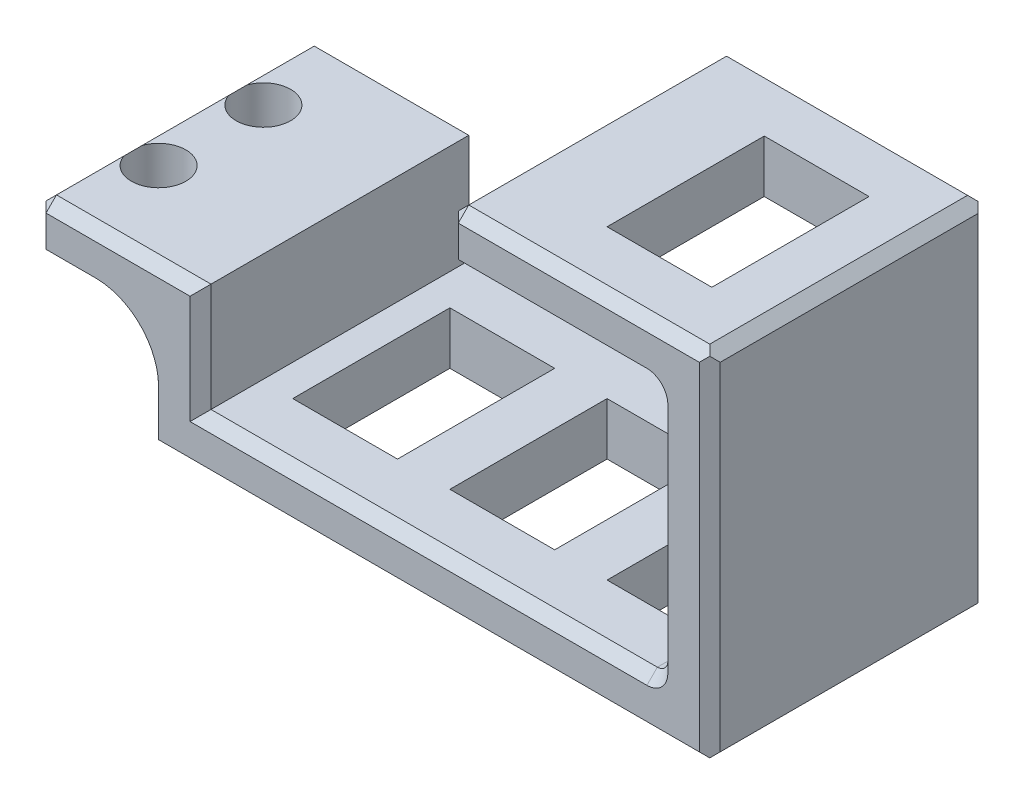
SolidWorks part; units mm, degrees
ref_plane "Alzado" through (0, 0, 0) normal (0, 0, 1) x (1, 0, 0)
ref_plane "Planta" through (0, 0, 0) normal (0, 1, 0) x (1, 0, 0)
ref_plane "Vista lateral" through (0, 0, 0) normal (1, 0, 0) x (0, 0, -1)
sketch "Croquis1" plane through (0, 0, 0) normal (0, 0, 1) x (1, 0, 0)
  line L1 (20.8029, -8) -> (36.55, -8)
  line L2 (20.8029, -8) -> (20.8029, -13)
  line L3 (20.8029, -13) -> (31.55, -13)
  line L6 (80.15, -18.36) -> (85.15, -18.36) construction
  line L8 (31.55, -13) -> (31.55, -23.36)
  line L9 (31.55, -23.36) -> (36.55, -23.36)
  line L10 (36.55, -8) -> (36.55, -18.36)
  line L12 (36.55, -23.36) -> (85.15, -23.36)
  line L14 (36.55, -18.36) -> (80.15, -18.36)
  line L15 (85.15, -23.36) -> (85.15, -18.36)
  line L17 (85.15, -18.36) -> (85.15, 10.84)
  line L18 (85.15, 10.84) -> (80.15, 10.84)
  line L19 (80.15, -18.36) -> (80.15, 5.84)
  line L20 (31.55, -13) -> (36.55, -13) construction
  line L21 (36.55, -23.36) -> (36.55, -18.36) construction
  line L24 (80.15, 10.84) -> (60.15, 10.84)
  line L26 (80.15, 5.84) -> (60.15, 5.84)
  line L27 (60.15, 10.84) -> (60.15, 5.84)
  line L29 (80.15, 10.84) -> (80.15, 5.84) construction
  line L31 (46.55, 5.64) -> (70.15, 5.64) construction
  line L32 (34.55, -8) -> (0, -8) construction
  line L33 (20.6029, -25.5) -> (20.6029, 2.44) construction
  line L34 (36.55, -13.36) -> (36.55, 0.64) construction
  line L35 (41.55, -18.36) -> (46.55, -18.36) construction
  line L36 (80.15, 0.64) -> (80.15, -13.36) construction
  dimension "D1" = 5
  dimension "D2" = 0.2
  dimension "D3" = 0.2
  dimension "D4" = 5
  dimension "D5" = 20
extrude "Saliente-Extruir1" add sketch "Croquis1" against normal up to surface (26.6 mm away) contours L19 L14 L10 L1 L2 L3 L8 L9 L12 L15 L17 L18 region at (28.6764, -8.7287, 0)
sketch "Croquis2" plane through (0, -8, 0) normal (0, 1, 0) x (1, 0, 0)
  circle A0 centre (24.25, 18.3) radius 2.6
  circle A1 centre (24.25, 8.3) radius 2.6
  arc A2 (26.1286, 9.6269) -> (26.1286, 6.9731) centre (24.25, 8.3) ccw construction
  arc A3 (26.1286, 19.6269) -> (26.1286, 16.9731) centre (24.25, 18.3) ccw construction
  dimension "D1" = 0.3
  dimension "D2" = 0.3
extrude "Cortar-Extruir1" cut sketch "Croquis2" against normal through all
fillet "Redondeo1" radius 5 1 edges at (31.55, -13, -13.3)
fillet "Redondeo2" radius 1 2 edges at (80.15, -18.36, -13.3) (80.15, 5.84, -13.3)
chamfer "Chaflán1" distance 1 angle 45 34 edges at (85.15, -6.26, 0) (58.35, -23.36, 0) (31.55, -20.68, 0) (30.0855, -14.4645, 0) (23.6764, -13, 0) (20.8029, -10.5, 0) (28.6764, -8, 0) (57.85, -18.36, 0) (79.8571, -18.0671, 0) (80.15, -6.26, 0) (79.8571, 5.5471, 0) (69.65, 5.84, 0) (60.15, 8.34, 0) (72.65, 10.84, 0) (60.15, 8.34, -26.6) (60.15, 5.84, -13.3) (69.65, 5.84, -26.6) (79.8571, 5.5471, -26.6) (80.15, -6.26, -26.6) (79.8571, -18.0671, -26.6) (57.85, -18.36, -26.6) (28.6764, -8, -26.6) (20.8029, -8, -13.3) (20.8029, -10.5, -26.6) (60.15, 10.84, -13.3) (72.65, 10.84, -26.6) (85.15, -6.26, -26.6) (58.35, -23.36, -26.6) (31.55, -20.68, -26.6) (30.0855, -14.4645, -26.6) (23.6764, -13, -26.6) (20.8029, -13, -13.3) (36.55, -13.18, 0) (36.55, -13.18, -26.6)
sketch "Croquis3" plane through (0, -23.36, 0) normal (0, -1, 0) x (1, 0, 0)
  line L0 (31.55, -13.3) -> (85.15, -13.3) construction
  line L1 (31.55, -25.6) -> (31.55, -1) construction
  line L2 (85.15, -25.6) -> (85.15, -1) construction
  line L3 (64.55, -20.8) -> (64.55, -5.8)
  line L4 (39.55, -20.8) -> (49.55, -20.8)
  line L5 (39.55, -20.8) -> (39.55, -5.8)
  line L6 (39.55, -5.8) -> (49.55, -5.8)
  line L7 (49.55, -20.8) -> (49.55, -5.8)
  line L8 (39.55, -20.8) -> (49.55, -5.8) construction
  line L9 (39.55, -5.8) -> (49.55, -20.8) construction
  line L10 (54.55, -20.8) -> (64.55, -20.8)
  line L11 (54.55, -20.8) -> (54.55, -5.8)
  line L12 (54.55, -5.8) -> (64.55, -5.8)
  line L13 (79.55, -20.8) -> (79.55, -5.8)
  line L14 (69.55, -20.8) -> (79.55, -20.8)
  line L15 (69.55, -20.8) -> (69.55, -5.8)
  line L16 (69.55, -5.8) -> (79.55, -5.8)
  point P6 (44.55, -13.3)
  dimension "D1" = 10
  dimension "D2" = 15
  dimension "D3" = 8
  dimension "D4" = 3
extrude "Cortar-Extruir2" cut sketch "Croquis3" against normal up to next
sketch "Croquis4" plane through (0, -23.36, 0) normal (0, -1, 0) x (1, 0, 0)
  line L0 (79.55, -20.8) -> (79.55, -5.8) construction
  line L1 (69.55, -20.8) -> (79.55, -20.8) construction
  line L2 (79.55, -5.8) -> (69.55, -5.8) construction
  line L3 (69.55, -5.8) -> (69.55, -20.8) construction
  line L4 (79.55, -20.8) -> (79.55, -5.8)
  line L5 (69.55, -20.8) -> (79.55, -20.8)
  line L6 (79.55, -5.8) -> (69.55, -5.8)
  line L7 (69.55, -5.8) -> (69.55, -20.8)
extrude "Cortar-Extruir3" cut sketch "Croquis4" against normal through all
chamfer "Chaflán2" distance 1 angle 45 2 edges at (85.15, 10.84, -13.3) (85.15, -23.36, -13.3)
